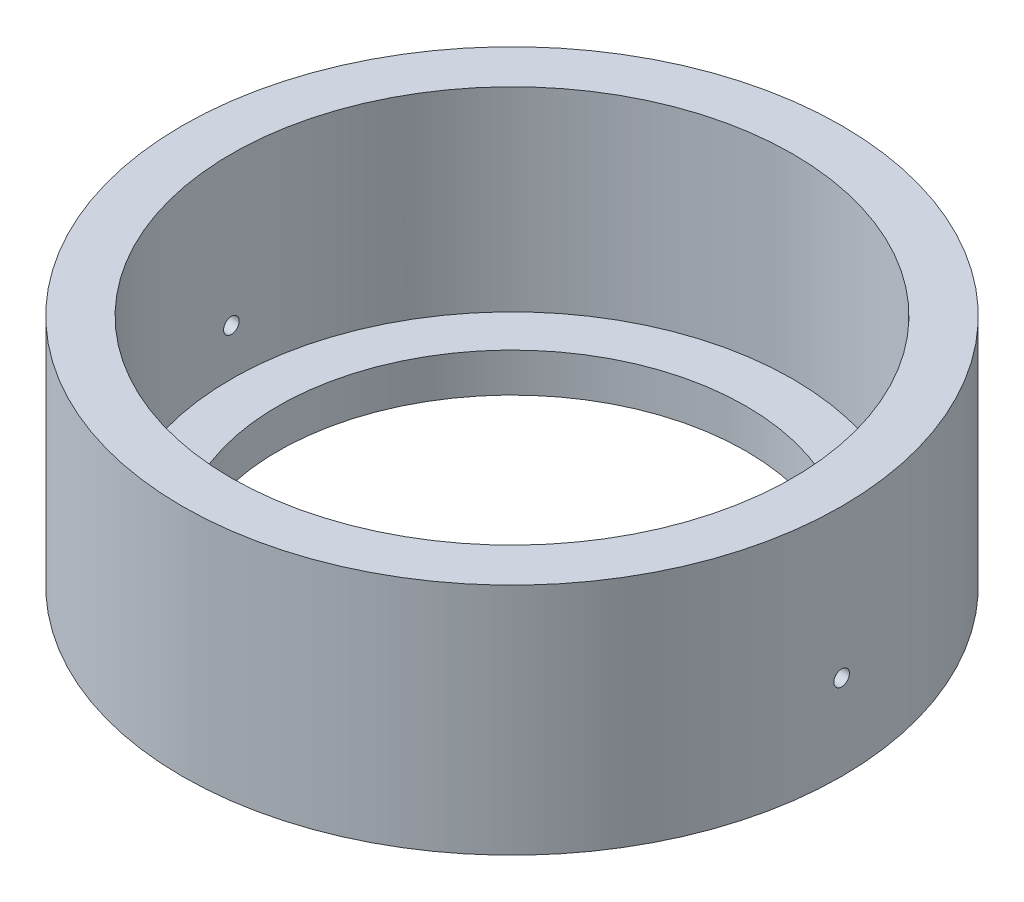
SolidWorks part; units mm, degrees
material "C (Graphite)"
ref_plane "Front Plane" through (0, 0, 0) normal (0, 0, 1) x (1, 0, 0)
ref_plane "Top Plane" through (0, 0, 0) normal (0, 1, 0) x (1, 0, 0)
ref_plane "Right Plane" through (0, 0, 0) normal (1, 0, 0) x (0, 0, -1)
sketch "Sketch1" plane through (0, 0, 0) normal (0, 1, 0) x (1, 0, 0)
  circle A0 centre (0, 0) radius 42.285
  circle A1 centre (0, 0) radius 36
  dimension "D1" = 84.57
  dimension "D2" = 72
extrude "Boss-Extrude1" add sketch "Sketch1" along normal blind 30
sketch "Sketch2" plane through (0, 0, 0) normal (0, -1, 0) x (1, 0, 0)
  circle A0 centre (0, 0) radius 37.5
  circle A1 centre (0, 0) radius 40
  dimension "D1" = 75
  dimension "D2" = 80
extrude "Cut-Extrude1" cut sketch "Sketch2" against normal blind 4.6
sketch "Sketch3" plane through (0, 0, 0) normal (1, 0, 0) x (0, 0, -1)
  line L0 (42.285, 30) -> (-42.285, 30) construction
  circle A0 centre (0, 10.95) radius 1
  dimension "D1" = 2
  dimension "D2" = 19.05
extrude "Cut-Extrude2" cut sketch "Sketch3" against normal through all both and the other way through all
sketch "Sketch4" plane through (0, 0, 0) normal (0, -1, 0) x (1, 0, 0)
  circle A0 centre (0, 0) radius 36.8189
  circle A1 centre (0, 0) radius 30
  dimension "D1" = 60
extrude "Boss-Extrude2" add sketch "Sketch4" against normal blind 5
